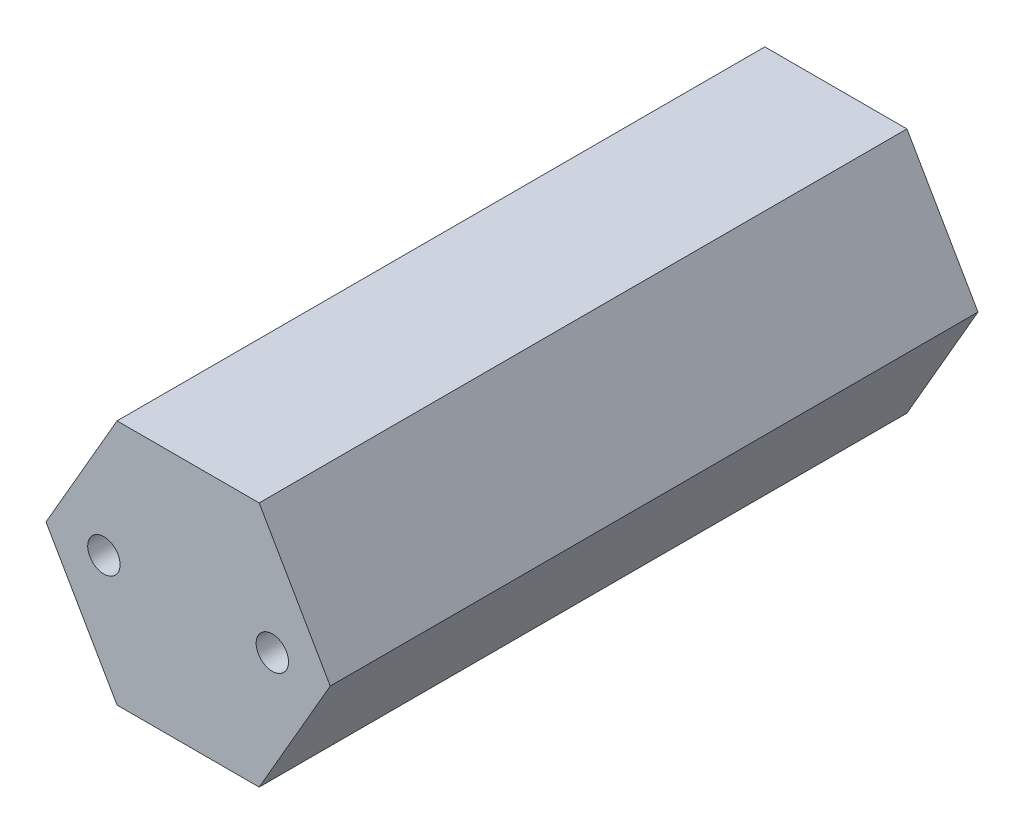
SolidWorks part; units mm, degrees
ref_plane "Front Plane" through (0, 0, 0) normal (0, 0, 1) x (1, 0, 0)
ref_plane "Top Plane" through (0, 0, 0) normal (0, 1, 0) x (1, 0, 0)
ref_plane "Right Plane" through (0, 0, 0) normal (1, 0, 0) x (0, 0, -1)
sketch "Sketch1" plane through (0, 0, 0) normal (0, 0, 1) x (1, 0, 0)
  line L1 (-5.4848, -9.5) -> (5.4848, -9.5)
  line L2 (5.4848, -9.5) -> (10.9697, 0)
  line L3 (10.9697, 0) -> (5.4848, 9.5)
  line L4 (5.4848, 9.5) -> (-5.4848, 9.5)
  line L5 (-5.4848, 9.5) -> (-10.9697, 0)
  line L6 (-10.9697, 0) -> (-5.4848, -9.5)
  circle A0 centre (0, 0) radius 9.5 construction
  circle A1 centre (-6.5, 0) radius 1.25
  circle A2 centre (-6.5, 0) radius 1.5 construction
  circle A3 centre (6.5, 0) radius 1.25
  circle A4 centre (6.5, 0) radius 1.5 construction
  point P20 (0, 0)
  dimension "D1" = 2.5
  dimension "D2" = 3
  dimension "D3" = 2
  dimension "D4" = 19
  dimension "D5" = 13
extrude "Boss-Extrude1" add sketch "Sketch1" along normal blind 50
